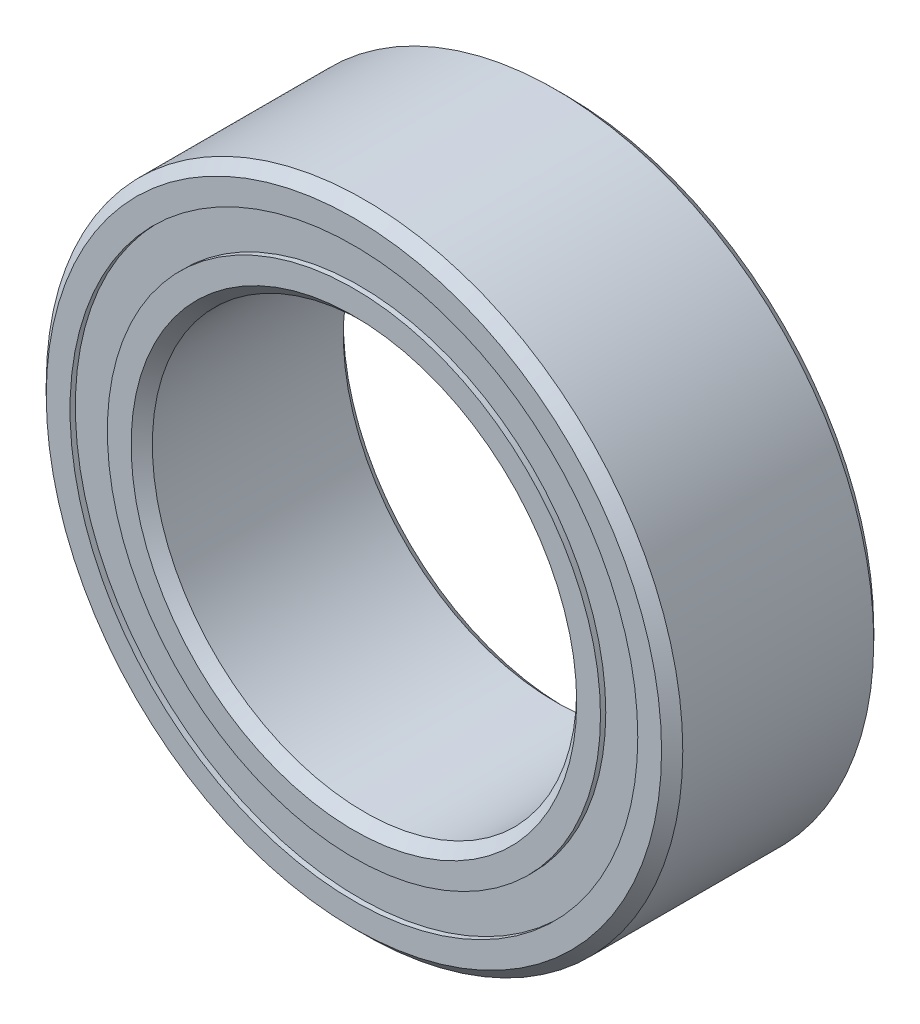
SolidWorks part; units mm, degrees
material "Cast Alloy Steel"
ref_plane "Front Plane" through (0, 0, 0) normal (0, 0, 1) x (1, 0, 0)
ref_plane "Top Plane" through (0, 0, 0) normal (0, 1, 0) x (1, 0, 0)
ref_plane "Right Plane" through (0, 0, 0) normal (1, 0, 0) x (0, 0, -1)
sketch "Sketch1" plane through (0, 0, 0) normal (1, 0, 0) x (0, 0, -1)
  line L0 (-1.5875, 0) -> (1.5875, 0) construction
  line L1 (0, 4.7625) -> (0, -4.7625) construction
  line L2 (1.4288, 4.7625) -> (-1.4288, 4.7625)
  line L3 (-1.4288, 4.7625) -> (-1.5875, 4.6037)
  line L4 (-1.5875, 4.6037) -> (-1.5875, 4.2479)
  line L5 (-1.5875, 4.2479) -> (-0.7056, 4.2479)
  line L6 (1.5875, 4.2479) -> (0.7056, 4.2479)
  line L7 (1.5875, 4.6037) -> (1.5875, 4.2479)
  line L8 (1.4288, 4.7625) -> (1.5875, 4.6037)
  line L9 (0, 4.7625) -> (0, 3.9688) construction
  line L10 (0, 3.9688) -> (0, 3.175) construction
  arc A0 (-0.7056, 4.2479) -> (0.7056, 4.2479) centre (0, 3.9688) cw
  point P14 (0, 3.175)
  dimension "D3" = 1.4111
  dimension "D1" = 45
  dimension "Width" = 3.175
  dimension "OD" = 9.525
  dimension "D2" = 0.1588
  dimension "Shaft Dia" = 6.35
  dimension "D4" = 0.2791
revolve "Revolve1" add sketch "Sketch1" angle 360 about L0
sketch "Sketch3" plane through (0, 0, 0) normal (1, 0, 0) x (0, 0, -1)
  line L0 (-0.7056, 3.6896) -> (-1.5875, 3.6896)
  line L1 (-1.5875, 4.6037) -> (-1.5875, 4.2479) construction
  line L2 (-1.4288, 4.7625) -> (-1.5875, 4.6037) construction
  line L3 (-1.5875, 3.6896) -> (-1.5875, 3.3337)
  line L5 (-1.5875, 3.3337) -> (-1.4288, 3.175)
  line L6 (-1.4288, 3.175) -> (1.4288, 3.175)
  line L7 (1.4288, 4.7625) -> (1.4288, -4.7625) construction
  line L8 (1.4288, 3.175) -> (1.5875, 3.3337)
  line L9 (1.5875, -4.6037) -> (1.5875, 4.6037) construction
  line L10 (1.5875, 3.3337) -> (1.5875, 3.6896)
  line L11 (1.5875, 3.6896) -> (0.7056, 3.6896)
  line L12 (0, 4.7625) -> (0, -4.7625) construction
  line L13 (1.4288, 4.7625) -> (1.5875, 4.6037) construction
  arc A1 (0.7056, 3.6896) -> (-0.7056, 3.6896) centre (0, 3.9687) cw
  arc A2 (0.7056, 4.2479) -> (-0.7056, 4.2479) centre (0, 3.9688) ccw construction
revolve "Revolve3" add sketch "Sketch3" angle 360 about L0
sketch "Sketch4" plane through (0, 0, 0) normal (1, 0, 0) x (0, 0, -1)
  line L0 (-0.7588, 3.9688) -> (0.7588, 3.9688)
  arc A2 (-0.7588, 3.9688) -> (0.7588, 3.9688) centre (0, 3.9688) cw
  arc A3 (0.7056, 4.2479) -> (-0.7056, 4.2479) centre (0, 3.9688) ccw construction
revolve "Revolve4" add sketch "Sketch4" angle 360 about L0
ref_axis "Axis1" through (0, 0, -1.5875) along (0, 0, 1)
pattern_circular "CirPattern1" count 12 every 30 about axis through (0, 0, -1.5875) along (0, 0, 1) of bodies 104
sketch "Sketch5" plane through (0, 0, 0) normal (1, 0, 0) x (0, 0, -1)
  line L0 (-1.5875, 4.2479) -> (-0.7056, 4.2479) construction
  line L1 (-1.5081, 4.2479) -> (-0.7588, 4.2479)
  line L2 (-1.5081, 4.2479) -> (-1.5081, 3.6896)
  line L3 (-1.5081, 3.6896) -> (-0.7588, 3.6896)
  line L4 (-0.7588, 4.2479) -> (-0.7588, 3.6896)
  line L5 (-0.7056, 3.6896) -> (-1.5875, 3.6896) construction
  line L6 (1.5875, 4.2479) -> (0.7056, 4.2479) construction
  line L7 (1.5081, 4.2479) -> (0.7588, 4.2479)
  line L8 (1.5081, 4.2479) -> (1.5081, 3.6896)
  line L9 (1.5081, 3.6896) -> (0.7588, 3.6896)
  line L10 (0.7588, 4.2479) -> (0.7588, 3.6896)
  line L11 (1.5875, 3.6896) -> (0.7056, 3.6896) construction
  line L12 (-1.4288, 4.7625) -> (-1.5875, 4.6037) construction
  point P18 (-1.5081, 4.6831)
revolve "Revolve5" add sketch "Sketch5" angle 360 about L0
equation "\"D2@Sketch1\" = \"Width@Sketch1\"*.05"
equation "\"D3@Sketch1\" = \"Width@Sketch1\"/2.25"
equation "\"D4@Sketch1\" = (((\"OD@Sketch1\"-\"Width@Sketch1\")/2)/3.25)/3.5"
equation "\"D2@CirPattern1\" = 360/\"Balls@CirPattern1\""
